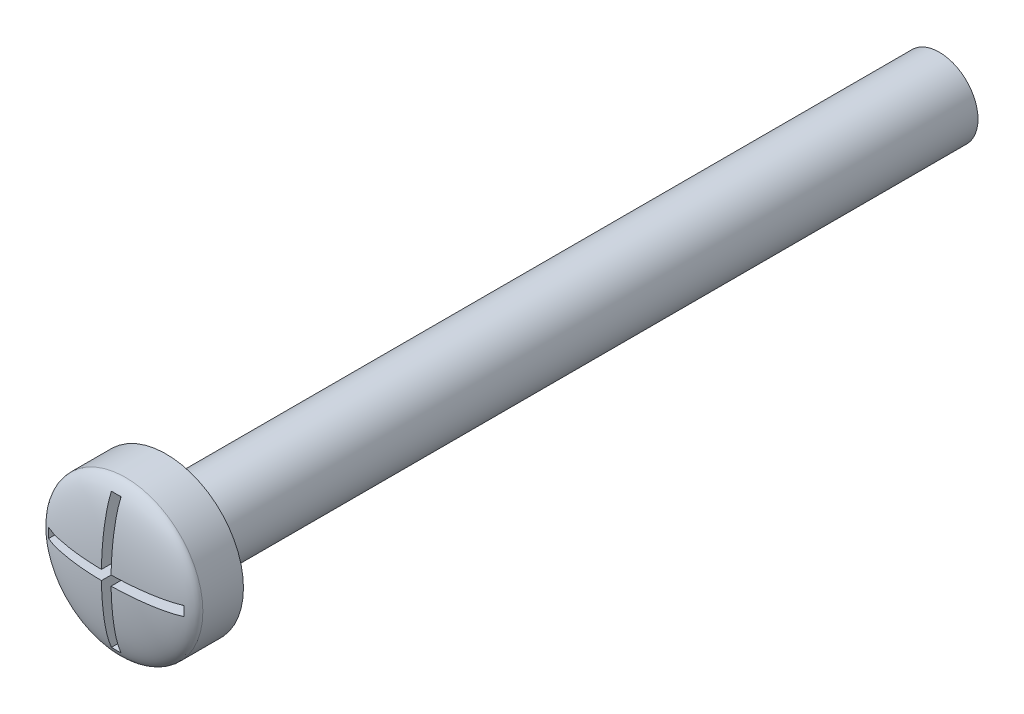
SolidWorks part; units mm, degrees
ref_plane "Front Plane" through (0, 0, 0) normal (0, 0, 1) x (1, 0, 0)
ref_plane "Top Plane" through (0, 0, 0) normal (0, 1, 0) x (1, 0, 0)
ref_plane "Right Plane" through (0, 0, 0) normal (1, 0, 0) x (0, 0, -1)
sketch "Sketch1" plane through (0, 0, 0) normal (0, 0, 1) x (1, 0, 0)
  circle A0 centre (0, 0) radius 4
  dimension "D1" = 8
extrude "Boss-Extrude3" add sketch "Sketch1" against normal blind 2.1 from offset 1 offset against normal yes
dome "Dome1" faces to dome 1 distance 1 reverse direction no elliptical dome yes face at (4, 0, -1) parameters "D1"=1
sketch "Sketch4" plane through (0, 0, -3.1) normal (0, 0, -1) x (-1, 0, 0)
  circle A0 centre (0, 0) radius 2
  dimension "D1" = 4
extrude "Boss-Extrude4" add sketch "Sketch4" along normal blind 40
sketch "Sketch5" plane through (0, 0, 0) normal (0, 0, 1) x (1, 0, 0)
  line L0 (0, 3.5) -> (0, -3.5) construction
  line L1 (-3.5, 0) -> (3.5, 0) construction
  line L2 (0, 3.5) -> (0, 4) construction
  line L3 (-0.25, 3.5) -> (0.25, 3.5)
  line L4 (-0.25, 3.5) -> (-0.25, -3.5)
  line L5 (-0.25, -3.5) -> (0.25, -3.5)
  line L6 (0.25, 3.5) -> (0.25, -3.5)
  line L7 (-3.5, 0.25) -> (3.5, 0.25)
  line L8 (-3.5, 0.25) -> (-3.5, -0.25)
  line L9 (-3.5, -0.25) -> (3.5, -0.25)
  line L10 (3.5, 0.25) -> (3.5, -0.25)
  circle A0 centre (0, 0) radius 4 construction
  point P6 (0, 0)
  dimension "D1" = 0.5
  dimension "D2" = 0.5
extrude "Cut-Extrude1" cut sketch "Sketch5" against normal blind 1 contours L8 L9 L4 L7 | L4 L9 L6 L7 | L4 L7 L6 L3 | L10 L7 L6 L9 | L9 L4 L5 L6 region at (0, 1.875, 0) region at (0, 0, 0) region at (-1.875, 0, 0) region at (1.875, 0, 0) region at (0, -1.875, 0)
